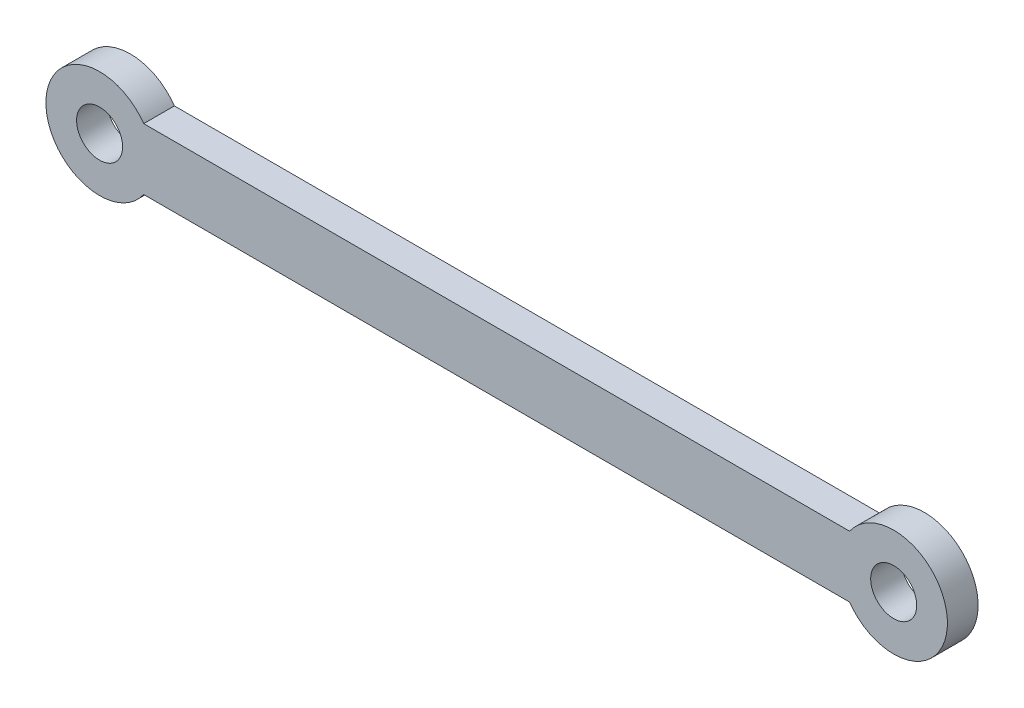
SolidWorks part; units mm, degrees
ref_plane "Alzado" through (0, 0, 0) normal (0, 0, 1) x (1, 0, 0)
ref_plane "Planta" through (0, 0, 0) normal (0, 1, 0) x (1, 0, 0)
ref_plane "Vista lateral" through (0, 0, 0) normal (1, 0, 0) x (0, 0, -1)
sketch "Croquis1" plane through (0, 0, 0) normal (0, 0, 1) x (1, 0, 0)
  line L0 (0, 0) -> (0, 50000) construction
  line L1 (0, 0) -> (50000, 0) construction
  line L2 (-23, -2) -> (23, -2)
  line L3 (-23, -2) -> (-23, 2)
  line L4 (-23, 2) -> (23, 2)
  line L5 (23, -2) -> (23, 2)
  line L6 (-23, -2) -> (23, 2) construction
  line L7 (-23, 2) -> (23, -2) construction
  circle A0 centre (-25.8723, 0) radius 3.5
  circle A1 centre (-25.8723, 0) radius 1.5
  circle A4 centre (25.8723, 0) radius 1.5
  circle A5 centre (25.8723, 0) radius 3.5
  point P5 (0, 0)
  dimension "D2" = 3
  dimension "D5" = 46
  dimension "D6" = 2
  dimension "D1" = 4
extrude "Saliente-Extruir1" add sketch "Croquis1" along normal blind 2 contours L2 A5 L4 A0 | L3 A0 A1 | A5 L5 A4 | L3 A0 | A5 L5 | A0 | A1 region at (0, 0, 0) region at (-29.2776, 0, 0) region at (-22.7469, 0, 0) region at (22.7469, 0, 0) region at (23.0947, 0, 0)
